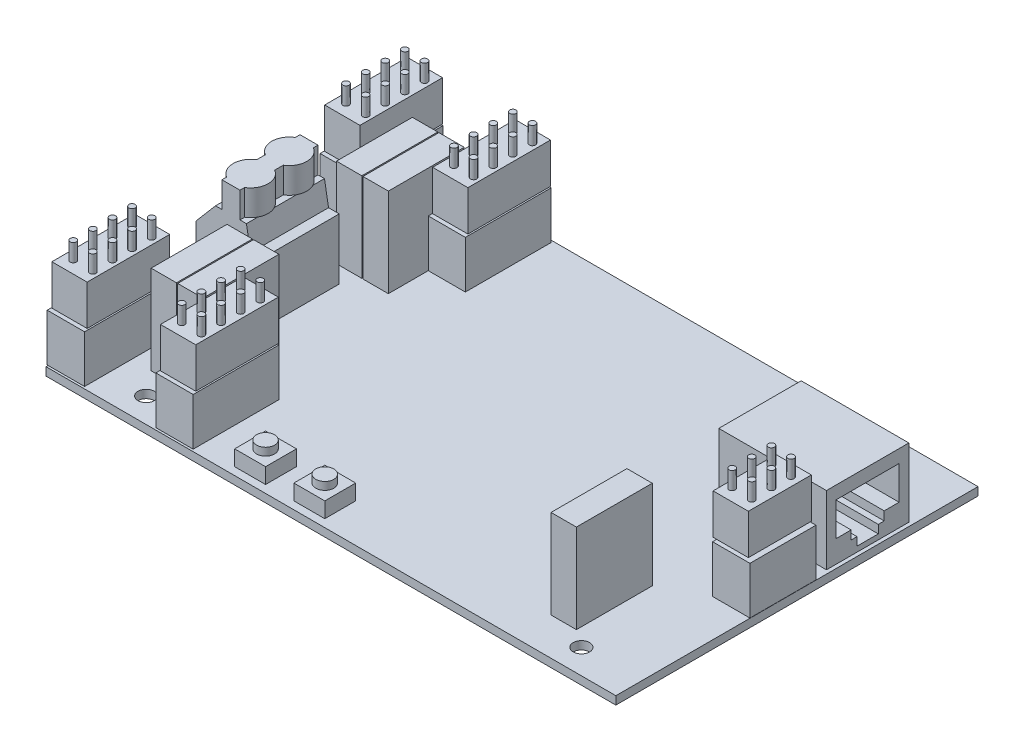
SolidWorks part; units mm, degrees
ref_plane "Front Plane" through (0, 0, 0) normal (0, 0, 1) x (1, 0, 0)
ref_plane "Top Plane" through (0, 0, 0) normal (0, 1, 0) x (1, 0, 0)
ref_plane "Right Plane" through (0, 0, 0) normal (1, 0, 0) x (0, 0, -1)
sketch "Sketch1" plane through (0, 0, 0) normal (0, 1, 0) x (1, 0, 0)
  line L0 (1.5775, 0) -> (0, 0) construction
  line L1 (-55.31, -35.15) -> (55.31, -35.15)
  line L2 (-55.31, -35.15) -> (-55.31, 35.15)
  line L3 (-55.31, 35.15) -> (55.31, 35.15)
  line L4 (55.31, -35.15) -> (55.31, 35.15)
  line L5 (-55.31, -35.15) -> (55.31, 35.15) construction
  line L6 (-55.31, 35.15) -> (55.31, -35.15) construction
  line L7 (-40.6725, -30.35) -> (43.8275, -30.35) construction
  line L8 (-40.6725, -30.35) -> (-40.6725, 30.35) construction
  line L9 (-40.6725, 30.35) -> (43.8275, 30.35) construction
  line L10 (43.8275, -30.35) -> (43.8275, 30.35) construction
  line L11 (-40.6725, -30.35) -> (43.8275, 30.35) construction
  line L12 (-40.6725, 30.35) -> (43.8275, -30.35) construction
  line L13 (-42.26, -30.35) -> (-55.31, -30.35) construction
  circle A0 centre (-40.6725, -30.35) radius 1.5875
  circle A1 centre (-40.6725, 30.35) radius 1.5875
  circle A2 centre (43.8275, 30.35) radius 1.5875
  circle A3 centre (43.8275, -30.35) radius 1.5875
  point P0 (0, 0)
  point P14 (0, 0)
  dimension "D3" = 3.175
  dimension "D6" = 4.8
  dimension "D7" = 70.3
  dimension "D1" = 13.05
  dimension "D2" = 110.62
  dimension "D4" = 84.5
  dimension "D5" = 60.7
extrude "Boss-Extrude1" add sketch "Sketch1" against normal blind 1.5875
sketch "Sketch2" plane through (0, 0, 0) normal (0, 1, 0) x (1, 0, 0)
  line L0 (-30.1535, -20.707) -> (-30.1535, -24.517) construction
  line L1 (-30.1535, -24.517) -> (-30.1535, -28.327) construction
  line L2 (-30.1535, -28.327) -> (-30.1535, -32.137) construction
  line L3 (51.0175, 1.137) -> (51.0175, -6.483) construction
  line L4 (51.0175, 1.137) -> (51.0175, -2.673) construction
  line L5 (-30.1535, 24.505) -> (-30.1535, 20.695) construction
  line L6 (-30.1535, 32.125) -> (-30.1535, 28.315) construction
  line L7 (-30.1535, 28.315) -> (-30.1535, 24.505) construction
  line L8 (-51.1085, 28.315) -> (-51.1085, 24.505) construction
  line L9 (-51.2355, -24.517) -> (-51.2355, -28.327) construction
  line L10 (-51.1085, 24.505) -> (-51.1085, 20.695) construction
  line L11 (-51.2355, -28.327) -> (-51.2355, -32.137) construction
  line L12 (-51.1085, 32.125) -> (-51.1085, 28.315) construction
  line L13 (-51.2355, -20.707) -> (-51.2355, -24.517) construction
  line L17 (55.31, 35.15) -> (-55.31, 35.15) construction
  line L19 (-55.1725, -34.55) -> (54.8275, -34.55) construction
  line L20 (-55.1725, -34.55) -> (-55.1725, 34.55) construction
  line L21 (-55.1725, 34.55) -> (54.8275, 34.55) construction
  line L22 (54.8275, -34.55) -> (54.8275, 34.55) construction
  circle A0 centre (51.0175, 1.137) radius 0.5
  circle A1 centre (51.0175, -2.673) radius 0.5
  circle A2 centre (51.0175, -6.483) radius 0.5
  circle A3 centre (-30.1535, -20.707) radius 0.5
  circle A4 centre (-30.1535, -24.517) radius 0.5
  circle A5 centre (-30.1535, -28.327) radius 0.5
  circle A6 centre (-30.1535, -32.137) radius 0.5
  circle A7 centre (-30.1535, 32.125) radius 0.5
  circle A8 centre (-30.1535, 20.695) radius 0.5
  circle A9 centre (-30.1535, 24.505) radius 0.5
  circle A10 centre (-30.1535, 28.315) radius 0.5
  circle A11 centre (-51.1085, 28.315) radius 0.5
  circle A12 centre (-51.1085, 24.505) radius 0.5
  circle A13 centre (-51.2355, -28.327) radius 0.5
  circle A14 centre (-51.2355, -20.707) radius 0.5
  circle A15 centre (-51.2355, -24.517) radius 0.5
  circle A16 centre (-51.1085, 32.125) radius 0.5
  circle A17 centre (-51.2355, -32.137) radius 0.5
  circle A18 centre (-51.1085, 20.695) radius 0.5
  circle A19 centre (-40.6725, -30.35) radius 1.5875 construction
  dimension "D1" = 3.937
  dimension "D2" = 14.5
  dimension "D3" = 1
  dimension "D4" = 25.019
  dimension "D5" = 3.81
  dimension "D6" = 4.064
  dimension "D7" = 14.455
  dimension "D8" = 25.019
  dimension "D9" = 69.1
  dimension "D11" = 13.843
  dimension "D10" = 66.675
  dimension "D12" = 4.2
  dimension "D15" = 35.687
  dimension "D13" = 110
  dimension "D14" = 3.81
extrude "Cut-Extrude1" cut sketch "Sketch2" against normal through all
sketch "Sketch3" plane through (0, 0, 0) normal (0, 1, 0) x (1, 0, 0)
  line L0 (55.31, 35.15) -> (-55.31, 35.15) construction
  line L1 (-44.42, -10.898) -> (-39.5, -10.898)
  line L2 (-44.42, -10.898) -> (-44.42, -25.63)
  line L3 (-44.42, -25.63) -> (-39.5, -25.63)
  line L4 (-39.5, -10.898) -> (-39.5, -25.63)
  line L5 (-44.42, -10.898) -> (-39.5, -25.63) construction
  line L6 (-44.42, -25.63) -> (-39.5, -10.898) construction
  line L11 (-39.27, -25.63) -> (-34.35, -25.63)
  line L12 (-39.27, -25.63) -> (-39.27, -10.898)
  line L13 (-39.27, -10.898) -> (-34.35, -10.898)
  line L14 (-34.35, -25.63) -> (-34.35, -10.898)
  line L15 (-39.27, -25.63) -> (-34.35, -10.898) construction
  line L16 (-39.27, -10.898) -> (-34.35, -25.63) construction
  line L17 (-39.27, 10.348) -> (-34.35, 10.348)
  line L18 (-39.27, 10.348) -> (-39.27, 25.08)
  line L19 (-39.27, 25.08) -> (-34.35, 25.08)
  line L20 (-34.35, 10.348) -> (-34.35, 25.08)
  line L21 (-39.27, 10.348) -> (-34.35, 25.08) construction
  line L22 (-39.27, 25.08) -> (-34.35, 10.348) construction
  line L23 (-44.42, 10.348) -> (-39.5, 10.348)
  line L24 (-44.42, 10.348) -> (-44.42, 25.08)
  line L25 (-44.42, 25.08) -> (-39.5, 25.08)
  line L26 (-39.5, 10.348) -> (-39.5, 25.08)
  line L27 (-44.42, 10.348) -> (-39.5, 25.08) construction
  line L28 (-44.42, 25.08) -> (-39.5, 10.348) construction
  line L29 (55.31, -35.15) -> (55.31, 35.15) construction
  line L32 (35.46, -13.148) -> (40.38, -13.148)
  line L33 (35.46, -13.148) -> (35.46, -27.88)
  line L34 (35.46, -27.88) -> (40.38, -27.88)
  line L35 (40.38, -13.148) -> (40.38, -27.88)
  line L36 (35.46, -13.148) -> (40.38, -27.88) construction
  line L37 (35.46, -27.88) -> (40.38, -13.148) construction
  line L38 (-55.31, -35.15) -> (55.31, -35.15) construction
  line L39 (-55.31, 35.15) -> (-55.31, -35.15) construction
  point P0 (-41.96, -18.264)
  point P5 (-36.81, -18.264)
  point P10 (-36.81, 17.714)
  point P15 (-41.96, 17.714)
  point P28 (37.92, -20.514)
  dimension "D1" = 14.732
  dimension "D2" = 10.07
  dimension "D3" = 9.52
  dimension "D4" = 4.92
  dimension "D5" = 10.89
  dimension "D6" = 10.07
  dimension "D7" = 7.27
  dimension "D8" = 50.71
  dimension "D9" = 14.93
  dimension "D10" = 19.85
extrude "Boss-Extrude2" add sketch "Sketch3" along normal blind 17.25
sketch "Sketch4" plane through (0, 0, 0) normal (0, 1, 0) x (1, 0, 0)
  line L0 (55.31, 35.15) -> (-55.31, 35.15) construction
  line L1 (-53.44, -7.95) -> (-40.74, -7.95)
  line L2 (-53.44, -7.95) -> (-53.44, 7.2)
  line L3 (-53.44, 7.2) -> (-40.74, 7.2)
  line L4 (-40.74, -7.95) -> (-40.74, 7.2)
  line L5 (-53.44, -7.95) -> (-40.74, 7.2) construction
  line L6 (-53.44, 7.2) -> (-40.74, -7.95) construction
  line L7 (-55.31, 35.15) -> (-55.31, -35.15) construction
  line L8 (-55.31, -35.15) -> (55.31, -35.15) construction
  point P0 (-47.09, -0.375)
  dimension "D1" = 15.15
  dimension "D2" = 12.7
  dimension "D3" = 1.87
  dimension "D4" = 27.95
  dimension "D5" = 27.2
extrude "Boss-Extrude3" add sketch "Sketch4" along normal blind 11.8
sketch "Sketch5" plane through (0, 0, 7.95) normal (0, 0, 1) x (1, 0, 0)
  line L0 (-53.44, 11.8) -> (-40.74, 11.8) construction
  line L1 (-53.44, 11.8) -> (-42.81, 11.8)
  line L2 (-53.44, 11.8) -> (-49.6035, 16.3)
  line L3 (-49.6035, 16.3) -> (-43.6035, 16.3)
  line L4 (-43.6035, 16.3) -> (-42.81, 11.8)
  line L6 (-40.74, 11.8) -> (-40.74, 0) construction
  line L8 (-53.44, 0) -> (-40.74, 0) construction
  dimension "D1" = 16.3
  dimension "D2" = 2.07
  dimension "D3" = 100
  dimension "D4" = 6
extrude "Boss-Extrude4" add sketch "Sketch5" against normal up to surface (15.15 mm away) up to face at (-47.09, 5.9, -7.2)
sketch "Sketch6" plane through (0, 16.3, 0) normal (0, 1, 0) x (1, 0, 0)
  line L0 (-49.6035, 7.2) -> (-43.6035, 7.2) construction
  line L1 (-48.3535, 7.2) -> (-44.8535, 7.2)
  line L2 (-48.3535, 7.2) -> (-48.3535, 6.29)
  line L3 (-48.3535, -7.95) -> (-44.8535, -7.95)
  line L4 (-44.8535, 7.2) -> (-44.8535, 6.29)
  line L5 (-43.6035, -7.95) -> (-49.6035, -7.95) construction
  line L6 (-46.6035, 3.375) -> (-46.6035, -4.125) construction
  line L7 (-44.8535, -0.375) -> (-48.3535, -0.375) construction
  line L8 (-48.3535, -7.04) -> (-48.3535, -7.95)
  line L9 (-48.3535, 0.46) -> (-48.3535, -1.21)
  line L10 (-44.8535, 0.46) -> (-44.8535, -1.21)
  line L11 (-44.8535, -7.04) -> (-44.8535, -7.95)
  arc A0 (-48.3535, -1.21) -> (-48.3535, -7.04) centre (-46.6035, -4.125) ccw
  arc A1 (-44.8535, 0.46) -> (-44.8535, 6.29) centre (-46.6035, 3.375) ccw
  arc A2 (-48.3535, 6.29) -> (-48.3535, 0.46) centre (-46.6035, 3.375) ccw
  arc A3 (-44.8535, -7.04) -> (-44.8535, -1.21) centre (-46.6035, -4.125) ccw
  point P8 (-46.6035, -7.95)
  point P15 (-46.6035, -0.375)
  dimension "D2" = 6.8
  dimension "D3" = 7.5
  dimension "D1" = 3.5
extrude "Boss-Extrude5" add sketch "Sketch6" along normal blind 5
sketch "Sketch7" plane through (0, 0, 0) normal (0, 1, 0) x (1, 0, 0)
  line L0 (55.31, 35.15) -> (-55.31, 35.15) construction
  line L1 (33.69, 6.45) -> (54.59, 6.45)
  line L2 (33.69, 6.45) -> (33.69, 22.45)
  line L3 (33.69, 22.45) -> (54.59, 22.45)
  line L4 (54.59, 6.45) -> (54.59, 22.45)
  line L5 (55.31, -35.15) -> (55.31, 35.15) construction
  dimension "D1" = 12.7
  dimension "D2" = 0.72
  dimension "D3" = 16
  dimension "D4" = 20.9
extrude "Boss-Extrude6" add sketch "Sketch7" along normal blind 13.33
sketch "Sketch8" plane through (54.59, 0, 0) normal (1, 0, 0) x (0, 0, -1)
  line L0 (16.51, 2.6125) -> (17.66, 2.6125)
  line L1 (8.35, 10.83) -> (20.55, 10.83)
  line L2 (8.35, 10.83) -> (8.35, 4.3125)
  line L3 (8.35, 4.3125) -> (11.24, 4.3125)
  line L4 (20.55, 10.83) -> (20.55, 4.3125)
  line L6 (11.24, 4.3125) -> (11.24, 2.6125)
  line L7 (11.24, 2.6125) -> (12.39, 2.6125)
  line L8 (17.66, 4.3125) -> (17.66, 2.6125)
  line L10 (12.39, 2.6125) -> (12.39, 1.0125)
  line L11 (12.39, 1.0125) -> (16.51, 1.0125)
  line L12 (16.51, 2.6125) -> (16.51, 1.0125)
  line L13 (17.66, 4.3125) -> (20.55, 4.3125)
  line L14 (14.45, 10.83) -> (14.45, 13.33) construction
  line L15 (6.45, 13.33) -> (22.45, 13.33) construction
  line L16 (6.45, 13.33) -> (6.45, 0) construction
  line L17 (-35.15, -1.5875) -> (35.15, -1.5875) construction
  dimension "D1" = 1.9
  dimension "D2" = 2.5
  dimension "D3" = 2.6
  dimension "D4" = 4.2
  dimension "D5" = 5.9
  dimension "D6" = 6.42
  dimension "D7" = 4.12
extrude "Cut-Extrude2" cut sketch "Sketch8" against normal blind 10.5
sketch "Sketch9" plane through (0, 0, 0) normal (0, 1, 0) x (1, 0, 0)
  line L0 (-55.31, -35.15) -> (55.31, -35.15) construction
  line L1 (-20.19, -27.65) -> (-14.19, -27.65)
  line L2 (-20.19, -27.65) -> (-20.19, -33.65)
  line L3 (-20.19, -33.65) -> (-14.19, -33.65)
  line L4 (-14.19, -27.65) -> (-14.19, -33.65)
  line L5 (-8.69, -27.65) -> (-2.69, -27.65)
  line L6 (-8.69, -27.65) -> (-8.69, -33.65)
  line L7 (-8.69, -33.65) -> (-2.69, -33.65)
  line L8 (-2.69, -27.65) -> (-2.69, -33.65)
  line L9 (55.31, -35.15) -> (55.31, 35.15) construction
  dimension "D1" = 6
  dimension "D2" = 1.5
  dimension "D3" = 17.5
  dimension "D4" = 58
extrude "Boss-Extrude7" add sketch "Sketch9" along normal blind 3
sketch "Sketch10" plane through (0, 3, 0) normal (0, 1, 0) x (1, 0, 0)
  line L0 (-14.19, -27.65) -> (-20.19, -33.65) construction
  line L1 (-2.69, -27.65) -> (-8.69, -33.65) construction
  circle A0 centre (-17.19, -30.65) radius 1.75
  circle A1 centre (-5.69, -30.65) radius 1.75
  dimension "D1" = 3.5
extrude "Boss-Extrude8" add sketch "Sketch10" along normal blind 1.5
sketch "Sketch11" plane through (0, 0, 0) normal (0, 1, 0) x (1, 0, 0)
  line L0 (-30.1535, -20.707) -> (-30.1535, -18.107) construction
  line L1 (-34.4035, 34.725) -> (-27.1535, 34.725)
  line L2 (-34.4035, 34.725) -> (-34.4035, 18.095)
  line L3 (-34.4035, 18.095) -> (-27.1535, 18.095)
  line L4 (-27.1535, 34.725) -> (-27.1535, 18.095)
  line L5 (-55.3585, 34.725) -> (-48.1085, 34.725)
  line L6 (-55.3585, 34.725) -> (-55.3585, 18.095)
  line L7 (-55.3585, 18.095) -> (-48.1085, 18.095)
  line L8 (-48.1085, 34.725) -> (-48.1085, 18.095)
  line L9 (-55.4855, -18.107) -> (-48.2355, -18.107)
  line L10 (-55.4855, -18.107) -> (-55.4855, -34.737)
  line L11 (-55.4855, -34.737) -> (-48.2355, -34.737)
  line L12 (-48.2355, -18.107) -> (-48.2355, -34.737)
  line L13 (-34.4035, -18.107) -> (-27.1535, -18.107)
  line L14 (-34.4035, -18.107) -> (-34.4035, -34.737)
  line L15 (-34.4035, -34.737) -> (-27.1535, -34.737)
  line L16 (-27.1535, -18.107) -> (-27.1535, -34.737)
  line L17 (48.0175, 3.737) -> (55.2675, 3.737)
  line L18 (48.0175, 3.737) -> (48.0175, -9.083)
  line L19 (48.0175, -9.083) -> (55.2675, -9.083)
  line L20 (55.2675, 3.737) -> (55.2675, -9.083)
  line L21 (-30.1535, -20.707) -> (-34.4035, -20.707) construction
  line L22 (-51.2355, -20.707) -> (-55.4855, -20.707) construction
  line L23 (-51.1085, 32.125) -> (-55.3585, 32.125) construction
  line L24 (-30.1535, 32.125) -> (-34.4035, 32.125) construction
  line L25 (-51.2355, -18.107) -> (-51.2355, -20.707) construction
  line L26 (-51.1085, 34.725) -> (-51.1085, 32.125) construction
  line L27 (-30.1535, 34.725) -> (-30.1535, 32.125) construction
  line L28 (-30.1535, 20.695) -> (-30.1535, 18.095) construction
  line L29 (-30.1535, -32.137) -> (-30.1535, -34.737) construction
  line L30 (51.0175, 1.137) -> (51.0175, 3.737) construction
  line L31 (51.0175, -6.483) -> (51.0175, -9.083) construction
  line L32 (51.0175, -6.483) -> (55.2675, -6.483) construction
  circle A0 centre (-30.1535, 32.125) radius 0.5 construction
  circle A1 centre (-51.1085, 32.125) radius 0.5 construction
  dimension "D3" = 3
  dimension "D1" = 7.25
  dimension "D2" = 2.6
extrude "Boss-Extrude9" add sketch "Sketch11" along normal blind 9.2
sketch "Sketch12" plane through (0, 9.2, 0) normal (0, 1, 0) x (1, 0, 0)
  line L0 (-54.8855, -26.422) -> (-55.4855, -26.422) construction
  line L1 (-54.8855, -18.407) -> (-48.0355, -18.407)
  line L2 (-54.8855, -18.407) -> (-54.8855, -34.437)
  line L3 (-54.8855, -34.437) -> (-48.0355, -34.437)
  line L4 (-48.0355, -18.407) -> (-48.0355, -34.437)
  line L5 (-55.4855, -18.107) -> (-55.4855, -34.737) construction
  line L7 (-54.7585, 18.395) -> (-47.9085, 18.395)
  line L8 (-54.7585, 18.395) -> (-54.7585, 34.425)
  line L9 (-54.7585, 26.41) -> (-55.3585, 26.41) construction
  line L10 (-47.9085, 18.395) -> (-47.9085, 34.425)
  line L11 (-54.7585, 34.425) -> (-47.9085, 34.425)
  line L12 (-55.3585, 34.725) -> (-55.3585, 18.095) construction
  line L13 (-33.8035, -34.437) -> (-26.9535, -34.437)
  line L14 (-33.8035, 18.395) -> (-33.8035, 34.425)
  line L15 (-26.9535, -18.407) -> (-26.9535, -34.437)
  line L16 (-33.8035, 18.395) -> (-26.9535, 18.395)
  line L17 (-26.9535, 18.395) -> (-26.9535, 34.425)
  line L18 (-33.8035, 26.41) -> (-34.4035, 26.41) construction
  line L19 (-33.8035, 34.425) -> (-26.9535, 34.425)
  line L20 (-33.8035, -26.422) -> (-34.4035, -26.422) construction
  line L21 (-33.8035, -18.407) -> (-33.8035, -34.437)
  line L22 (-33.8035, -18.407) -> (-26.9535, -18.407)
  line L23 (-34.4035, -25.63) -> (-34.4035, -34.737) construction
  line L24 (-34.4035, 34.725) -> (-34.4035, 25.08) construction
  line L25 (47.8175, -8.783) -> (47.8175, 3.437)
  line L26 (47.8175, 3.437) -> (54.6675, 3.437)
  line L27 (54.6675, -2.673) -> (55.2675, -2.673) construction
  line L28 (47.8175, -8.783) -> (54.6675, -8.783)
  line L29 (54.6675, -8.783) -> (54.6675, 3.437)
  line L30 (-48.2355, -34.737) -> (-48.2355, -18.107) construction
  line L33 (55.2675, -9.083) -> (55.2675, 3.737) construction
  dimension "D1" = 16.03
  dimension "D2" = 6.85
  dimension "D3" = 12.22
  dimension "D4" = 0.2
extrude "Boss-Extrude10" add sketch "Sketch12" along normal offset from surface (7.8 mm away) 17.5 from offset 0.5 separate body up to face at (-33.7943, 0, 22.343) offset beyond the face yes
sketch "Sketch13" plane through (0, 17.5, 0) normal (0, 1, 0) x (1, 0, 0)
  line L0 (-28.1535, 34.425) -> (-28.1535, 32.125) construction
  line L1 (-33.8035, 34.425) -> (-26.9535, 34.425) construction
  line L2 (-28.1535, 32.125) -> (-26.9535, 32.125) construction
  line L3 (-26.9535, 34.425) -> (-26.9535, 18.395) construction
  line L4 (-49.1085, 34.425) -> (-49.1085, 32.125) construction
  line L5 (-54.7585, 34.425) -> (-47.9085, 34.425) construction
  line L6 (-49.1085, 32.125) -> (-47.9085, 32.125) construction
  line L7 (-47.9085, 34.425) -> (-47.9085, 18.395) construction
  line L8 (-49.2355, -18.407) -> (-49.2355, -20.707) construction
  line L9 (-54.8855, -18.407) -> (-48.0355, -18.407) construction
  line L10 (-49.2355, -20.707) -> (-48.0355, -20.707) construction
  line L11 (-48.0355, -18.407) -> (-48.0355, -34.437) construction
  line L12 (-28.1535, -18.407) -> (-28.1535, -20.707) construction
  line L13 (-33.8035, -18.407) -> (-26.9535, -18.407) construction
  line L14 (-28.1535, -20.707) -> (-26.9535, -20.707) construction
  line L15 (-26.9535, -18.407) -> (-26.9535, -34.437) construction
  line L16 (48.0175, -6.483) -> (49.2175, -6.483) construction
  line L17 (49.2175, -6.483) -> (53.0275, -6.483) construction
  line L18 (48.0175, 3.737) -> (48.0175, -9.083) construction
  line L19 (49.2175, 1.137) -> (49.2175, 3.437) construction
  line L20 (49.2175, -6.483) -> (49.2175, -8.783) construction
  line L21 (54.6675, -8.783) -> (47.8175, -8.783) construction
  line L22 (-49.1085, 32.125) -> (-52.9185, 32.125) construction
  line L23 (-28.1535, 20.695) -> (-28.1535, 18.395) construction
  line L24 (-26.9535, 18.395) -> (-33.8035, 18.395) construction
  line L25 (47.8175, 3.437) -> (54.6675, 3.437) construction
  circle A0 centre (-49.2355, -20.707) radius 0.6
  circle A1 centre (-28.1535, -20.707) radius 0.6
  circle A2 centre (-28.1535, 32.125) radius 0.6
  circle A3 centre (-49.1085, 32.125) radius 0.6
  circle A5 centre (49.2175, -6.483) radius 0.6
  circle A6 centre (-52.9185, 32.125) radius 0.6
  circle A7 centre (-31.9635, 32.125) radius 0.6
  circle A8 centre (-53.0455, -20.707) radius 0.6
  circle A9 centre (-31.9635, -20.707) radius 0.6
  circle A10 centre (-52.9185, 28.315) radius 0.6
  circle A11 centre (-31.9635, 28.315) radius 0.6
  circle A12 centre (-53.0455, -24.517) radius 0.6
  circle A13 centre (-31.9635, -24.517) radius 0.6
  circle A14 centre (-52.9185, 24.505) radius 0.6
  circle A15 centre (-31.9635, 24.505) radius 0.6
  circle A16 centre (-53.0455, -28.327) radius 0.6
  circle A17 centre (-31.9635, -28.327) radius 0.6
  circle A18 centre (-52.9185, 20.695) radius 0.6
  circle A19 centre (-31.9635, 20.695) radius 0.6
  circle A20 centre (-53.0455, -32.137) radius 0.6
  circle A21 centre (-31.9635, -32.137) radius 0.6
  circle A22 centre (-49.1085, 28.315) radius 0.6
  circle A23 centre (-28.1535, 28.315) radius 0.6
  circle A24 centre (-49.2355, -24.517) radius 0.6
  circle A25 centre (-28.1535, -24.517) radius 0.6
  circle A26 centre (-49.1085, 24.505) radius 0.6
  circle A27 centre (-28.1535, 24.505) radius 0.6
  circle A28 centre (-49.2355, -28.327) radius 0.6
  circle A29 centre (-28.1535, -28.327) radius 0.6
  circle A30 centre (-49.1085, 20.695) radius 0.6
  circle A31 centre (-28.1535, 20.695) radius 0.6
  circle A32 centre (-49.2355, -32.137) radius 0.6
  circle A33 centre (-28.1535, -32.137) radius 0.6
  circle A34 centre (53.0275, -6.483) radius 0.6
  circle A35 centre (53.0275, -2.673) radius 0.6
  circle A36 centre (53.0275, 1.137) radius 0.6
  circle A37 centre (49.2175, -2.673) radius 0.6
  circle A38 centre (49.2175, 1.137) radius 0.6
  dimension "D1" = 1.2
  dimension "D3" = 2.3
  dimension "D2" = 1.2
  dimension "D6" = 3.81
  dimension "D9" = 3.81
  dimension "D4" = 2
  dimension "D5" = 4
  dimension "D7" = 2
  dimension "D8" = 3
extrude "Boss-Extrude11" add sketch "Sketch13" along normal blind 3.4
